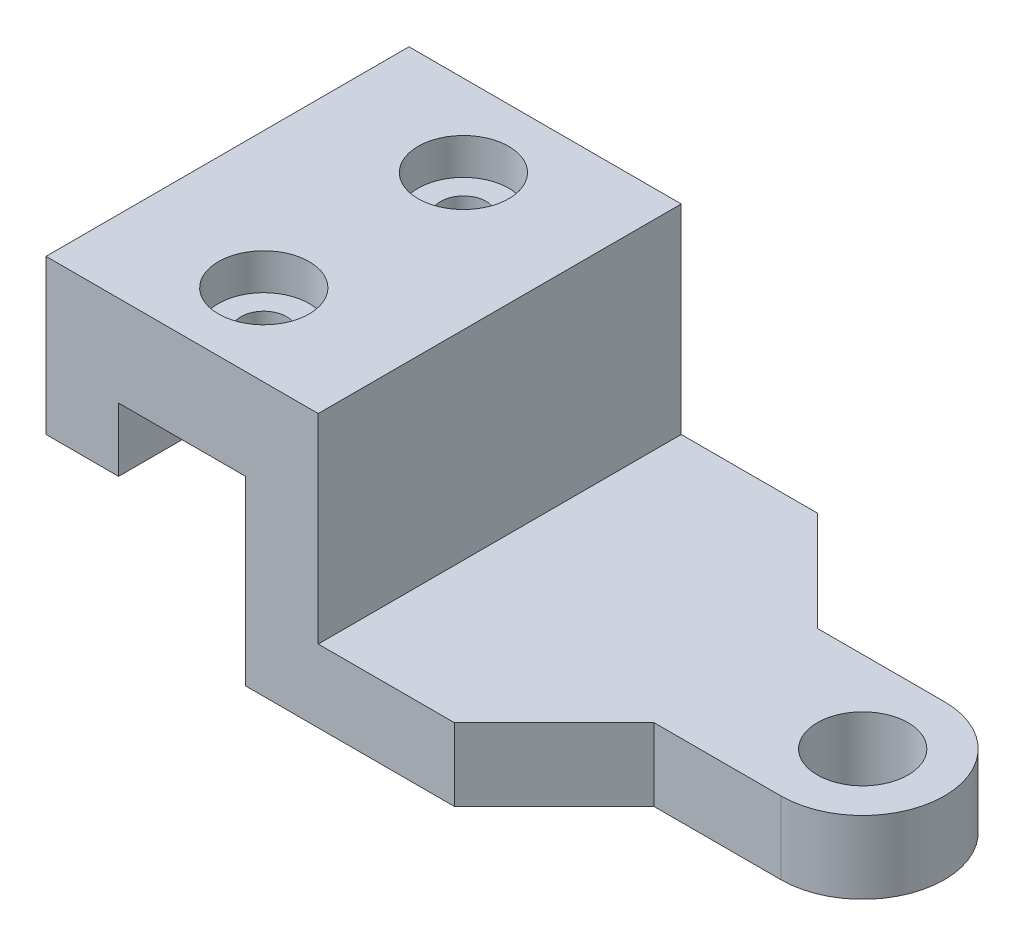
SolidWorks part; units mm, degrees
ref_plane "Front Plane" through (0, 0, 0) normal (0, 0, 1) x (1, 0, 0)
ref_plane "Top Plane" through (0, 0, 0) normal (0, 1, 0) x (1, 0, 0)
ref_plane "Right Plane" through (0, 0, 0) normal (1, 0, 0) x (0, 0, -1)
sketch "Sketch1" plane through (0, 0, 0) normal (0, 1, 0) x (1, 0, 0)
  line L0 (0, 0) -> (75, 0)
  line L1 (75, 0) -> (130, 55)
  line L2 (130, 55) -> (200, 55)
  line L3 (0, 0) -> (0, 200)
  line L4 (0, 200) -> (75, 200)
  line L5 (75, 200) -> (130, 145)
  line L6 (130, 145) -> (200, 145)
  line L8 (0, 0) -> (-150, 0)
  line L9 (0, 0) -> (0, 200)
  line L10 (0, 200) -> (-150, 200)
  line L11 (-150, 0) -> (-150, 200)
  line L12 (0, 0) -> (-150, 200) construction
  line L13 (0, 200) -> (-150, 0) construction
  line L14 (0, 200) -> (-40, 200)
  line L15 (0, 200) -> (0, 0)
  line L16 (0, 0) -> (-40, 0)
  line L17 (-40, 200) -> (-40, 0)
  line L18 (0, 200) -> (-40, 0) construction
  line L19 (0, 0) -> (-40, 200) construction
  arc A0 (200, 145) -> (200, 55) centre (200, 100) cw
  circle A1 centre (200, 100) radius 25
  point P11 (-75, 100)
  point P20 (-20, 100)
  dimension "D5" = 50
  dimension "D6" = 45
  dimension "D1" = 200
  dimension "D2" = 225
  dimension "D3" = 280
  dimension "D4" = 350
  dimension "D7" = 100
  dimension "D8" = 150
  dimension "D9" = 40
  dimension "D10" = 75
  dimension "D11" = 130
extrude "Boss-Extrude1" add sketch "Sketch1" along normal blind 40 contours A0 L6 L5 L4 L3 L0 L1 L2 A1 region at (88.4133, 0, -100)
extrude "Boss-Extrude2" add sketch "Sketch1<3>" along normal blind 150 contours L10 L17 L8 L3 region at (-20, 0, -100)
sketch "Sketch1<3>" plane through (0, 0, 0) normal (0, 1, 0) x (1, 0, 0) same geometry as "Sketch1"
sketch "Sketch2" plane through (-40, 0, 0) normal (-1, 0, 0) x (0, 0, 1)
  line L0 (0, 150) -> (0, 0) construction
  line L1 (-200, 150) -> (0, 150)
  line L2 (-200, 150) -> (-200, 100)
  line L3 (-200, 100) -> (0, 100)
  line L4 (0, 150) -> (0, 100)
  line L5 (-200, 150) -> (0, 100) construction
  line L6 (-200, 100) -> (0, 150) construction
  point P4 (-100, 125)
extrude "Boss-Extrude3" add sketch "Sketch2" along normal blind 110
sketch "Sketch3" plane through (0, 100, 0) normal (0, -1, 0) x (1, 0, 0)
  line L0 (-150, -200) -> (-40, -200) construction
  line L1 (-150, 0) -> (-110, 0)
  line L2 (-150, 0) -> (-150, -200)
  line L3 (-150, -200) -> (-110, -200)
  line L4 (-110, 0) -> (-110, -200)
  line L5 (-150, 0) -> (-110, -200) construction
  line L6 (-150, -200) -> (-110, 0) construction
  point P4 (-130, -100)
extrude "Boss-Extrude4" add sketch "Sketch3" along normal blind 35
sketch "Sketch6" plane through (0, 150, 0) normal (0, 1, 0) x (1, 0, 0)
  point P0 (-75, 155)
  point P2 (-75, 45)
hole_wizard "CBORE for M5 Hex Head Bolt1" positions "Sketch6" profile "Sketch7" counterbore size "M5" standard "ANSI Metric" end condition through all
sketch "Sketch7" plane through (-75, 150, -155) normal (1, 0, 0) x (0, 0, 1)
  line L0 (0, 0) -> (0, 150)
  line L1 (0, 150) -> (12.5, 150)
  line L3 (12.5, 150) -> (12.5, 20)
  line L4 (12.5, 20) -> (25, 20)
  line L5 (25, 20) -> (25, 0)
  line L7 (25, 0) -> (0, 0)
  line L11 (0, -6.35) -> (0, 107.95) construction
  dimension "Thru Hole Dia." = 25
  dimension "Thru Hole Depth" = 150
  dimension "C'Bore Dia." = 50
  dimension "C'Bore Depth" = 20
